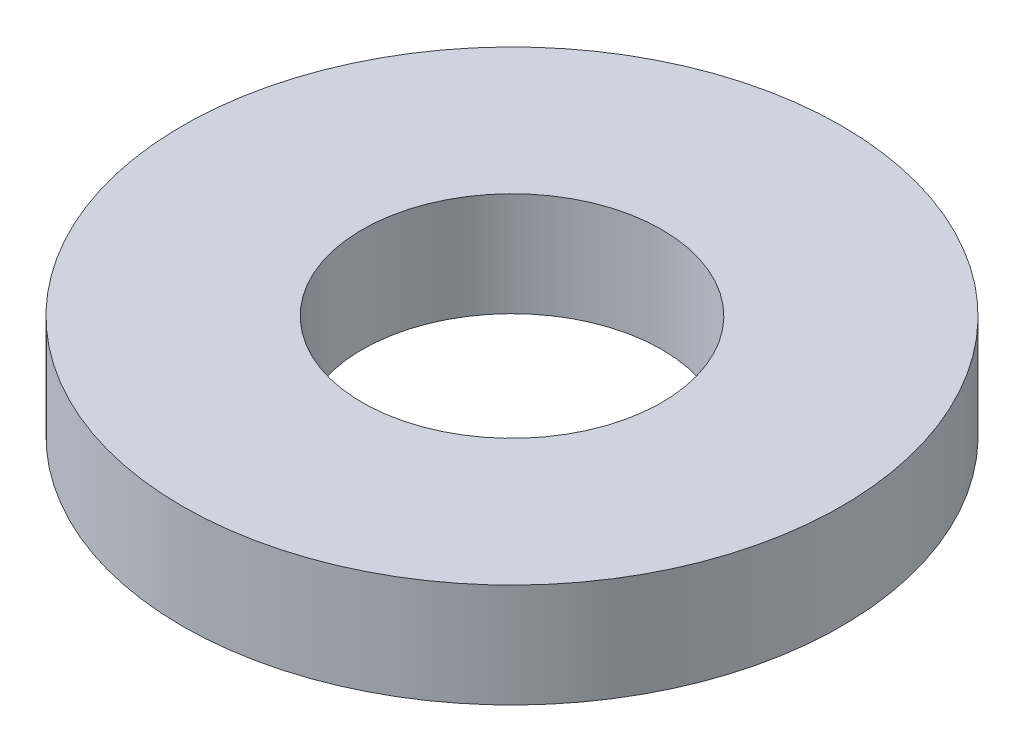
SolidWorks part; units mm, degrees
ref_plane "Front Plane" through (0, 0, 0) normal (0, 0, 1) x (1, 0, 0)
ref_plane "Top Plane" through (0, 0, 0) normal (0, 1, 0) x (1, 0, 0)
ref_plane "Right Plane" through (0, 0, 0) normal (1, 0, 0) x (0, 0, -1)
sketch "Sketch1" plane through (0, 0, 0) normal (0, 1, 0) x (1, 0, 0)
  circle A0 centre (0, 0) radius 82.5
  dimension "FLANGE_OD" = 165
extrude "Boss-Extrude1" add sketch "Sketch1" along normal blind 26
sketch "Sketch2" plane through (0, 0, 0) normal (0, 1, 0) x (1, 0, 0)
  circle A0 centre (0, 0) radius 37.5
  dimension "BORE_D" = 75
extrude "Cut-Extrude1" cut sketch "Sketch2" along normal through all
sketch "Sketch3" plane through (0, 26, 0) normal (0, 1, 0) x (1, 0, 0)
  circle A0 centre (0, 0) radius 29.5262 construction
  circle A1 centre (-29.5262, 0) radius 4.86
  dimension "BOLT_D" = 9.7199
  dimension "BOLT_PCD" = 59.0523
extrude "Cut-Extrude2" cut sketch "Sketch3" against normal blind 24.6452 rebuild error yes
pattern_circular "CirPattern1" count 3 over 360 rebuild error yes
